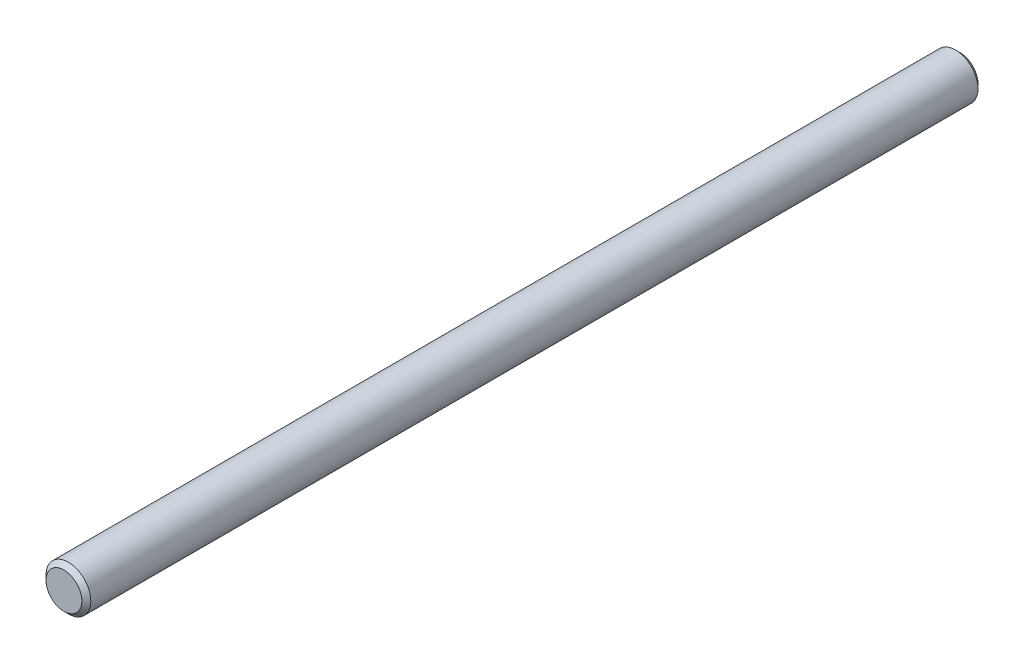
SolidWorks part; units mm, degrees
ref_plane "Front" through (0, 0, 0) normal (0, 0, 1) x (1, 0, 0)
ref_plane "Top" through (0, 0, 0) normal (0, 1, 0) x (1, 0, 0)
ref_plane "Right" through (0, 0, 0) normal (1, 0, 0) x (0, 0, -1)
sketch "Skizze1" plane through (0, 0, 0) normal (0, 0, 1) x (1, 0, 0)
  circle A0 centre (0, 0) radius 2.5
  dimension "D1" = 5
extrude "Aufsatz-Linear austragen1" add sketch "Skizze1" along normal blind 100
chamfer "Fase1" distance 0.5 angle 45 2 edges at (2.5, 0, 0) (2.5, 0, 100)
ref_axis "Axis1" through (0, 0, 99.5) along (0, 0, -1)
